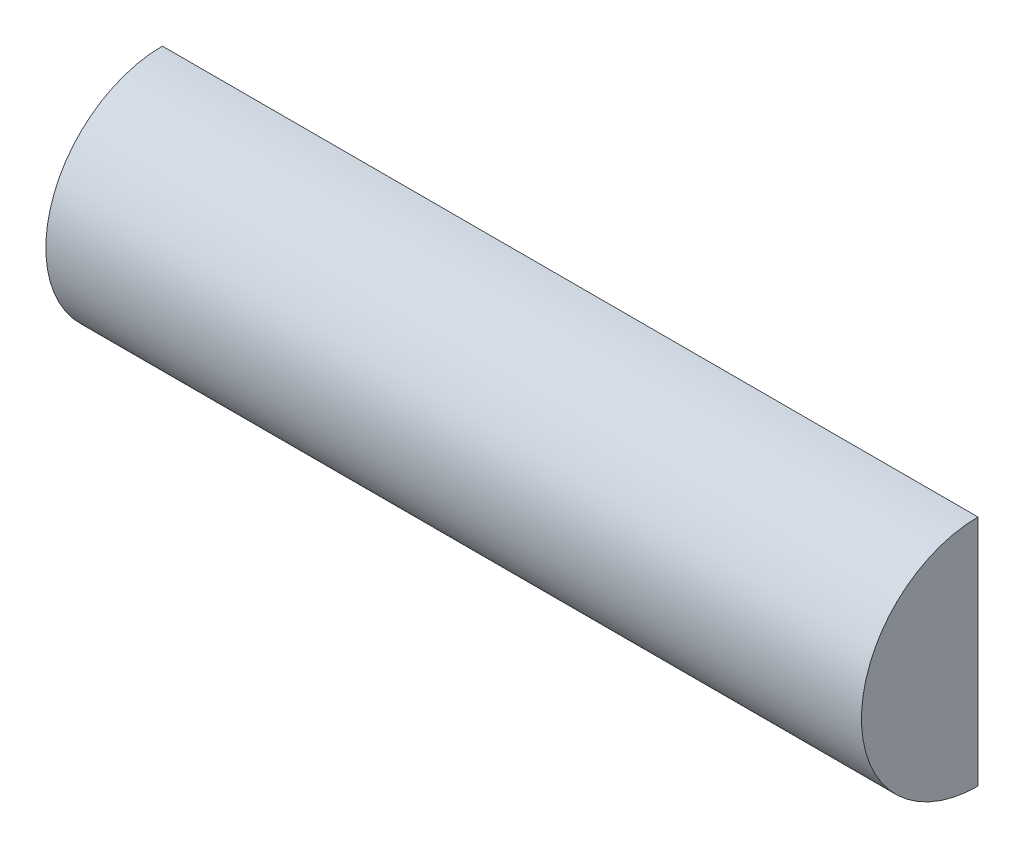
SolidWorks part; units mm, degrees
ref_plane "Front Plane" through (0, 0, 0) normal (0, 0, 1) x (1, 0, 0)
ref_plane "Top Plane" through (0, 0, 0) normal (0, 1, 0) x (1, 0, 0)
ref_plane "Right Plane" through (0, 0, 0) normal (1, 0, 0) x (0, 0, -1)
sketch "Sketch1" plane through (0, 0, 0) normal (0, 0, 1) x (1, 0, 0)
  line L0 (-668.9542, 0) -> (1072.3595, 0) construction
  line L1 (500, 0) -> (500, 40)
  line L2 (500, 40) -> (-350, 40)
  line L3 (-502, 0) -> (500, 0)
  arc A0 (-350, 40) -> (-500, 2.5) centre (-350, -278.75) ccw
  arc A1 (-500, 2.5) -> (-502, 0) centre (-498.093, -1.0756) ccw
  dimension "D1" = 80
  dimension "D2" = 150
  dimension "D3" = 1000
  dimension "D4" = 5
  dimension "D5" = 2
  dimension "D6" = 500
revolve "Forebody" add sketch "Sketch1" angle 180 about L0
sketch "Sketch2" plane through (0, 0, 0) normal (0, 0, 1) x (1, 0, 0)
  line L1 (-10000, 5000) -> (25000, 5000)
  line L2 (-10000, 5000) -> (-10000, 0)
  line L3 (-10000, 0) -> (25000, 0)
  line L4 (25000, 5000) -> (25000, 0)
  dimension "D1" = 5000
  dimension "D2" = 10000
  dimension "D3" = 25000
revolve "Fluid" add sketch "Sketch2" angle 180 about L3
sketch "Sketch4" plane through (0, 0, 0) normal (0, 0, 1) x (1, 0, 0)
  line L0 (-622, 0) -> (3000, 0)
  line L1 (3000, 0) -> (3000, 120)
  line L2 (3000, 120) -> (-502, 120)
  line L4 (-502, 0) -> (500, 0) construction
  arc A0 (-502, 120) -> (-622, 0) centre (-502, 0) ccw
  dimension "D2" = 3000
  dimension "D1" = 120
revolve "BOI" add sketch "Sketch4" angle 180 about L0
equation "\"Diameter\"=80"
equation "\"LengthCone\"=57.2246"
equation "\"LengthReference\"=1000"
equation "\"D6@Sketch1\"=\"LengthReference\"/2"
equation "\"D3@Sketch1\"=\"LengthReference\""
equation "\"D1@Sketch1\"=\"Diameter\""
equation "\"radialStream\"= \"LengthReference\" * 5"
equation "\"D1@Sketch2\"=\"radialStream\""
equation "\"lengthUpstream\"= \"LengthReference\" * 10"
equation "\"D2@Sketch2\"=\"lengthUpstream\""
equation "\"lengthDownstream\"= \"LengthReference\" * 25"
equation "\"D3@Sketch2\"=\"lengthDownstream\""
equation "\"radialBOI\"= \"Diameter\" * 1.5"
equation "\"downstreamBOI\"= \"LengthReference\" * 3"
equation "\"D2@Sketch4\"=\"downstreamBOI\""
equation "\"D1@Sketch4\"=\"radialBOI\""
